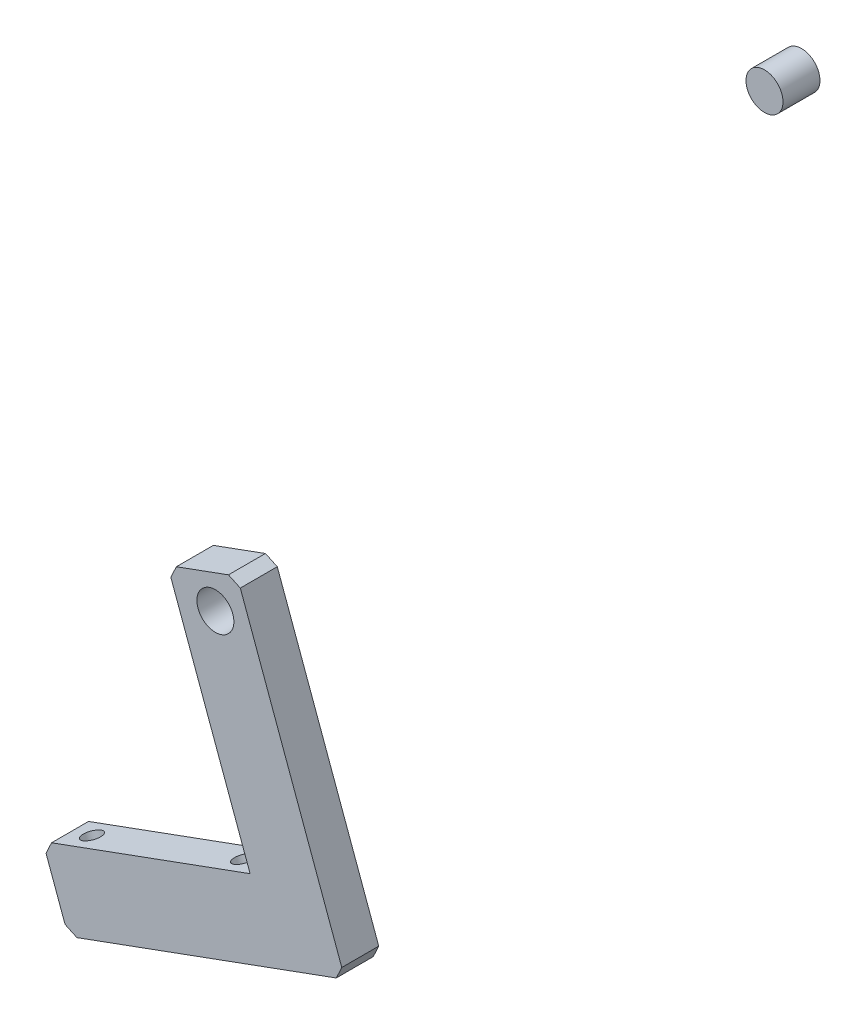
SolidWorks part; units mm, degrees
ref_plane "前基準面" through (0, 0, 0) normal (0, 0, 1) x (1, 0, 0)
ref_plane "上基準面" through (0, 0, 0) normal (0, 1, 0) x (1, 0, 0)
ref_plane "右基準面" through (0, 0, 0) normal (1, 0, 0) x (0, 0, -1)
sketch "草圖1" plane through (0, 0, 0) normal (0, 0, 1) x (1, 0, 0)
  line L0 (-29.9561, 9.7552) -> (-48.7426, 2.8947)
  line L2 (-48.7426, 2.8947) -> (-26.446, -58.1615)
  line L3 (-26.446, -58.1615) -> (-82.4902, -78.6278)
  line L4 (-82.4902, -78.6278) -> (-75.6297, -97.4144)
  line L5 (-75.6297, -97.4144) -> (-0.799, -70.0876)
  line L6 (-0.799, -70.0876) -> (-29.9561, 9.7552)
  circle A0 centre (-35.8357, -1.3461) radius 5
  circle A1 centre (112.659, 194.6505) radius 5
  dimension "D4" = 10
  dimension "D5" = 10
  dimension "D1" = 20
  dimension "D2" = 20
  dimension "D3" = 65
extrude "填料-伸長1" add sketch "草圖1" along normal blind 10
sketch "草圖2" plane through (15.6286, -42.7967, 0) normal (-0.343, 0.9393, 0) x (0.9393, 0.343, 0)
  circle A0 centre (-95.6715, -4.9822) radius 2.5
  circle A1 centre (-52.1263, -4.9822) radius 2.5
  dimension "D1" = 5
  dimension "D2" = 5
extrude "除料-伸長2" cut sketch "草圖2" against normal through all
chamfer "導角1" distance 2.5 angle 45 5 edges at (-29.9561, 9.7552, 5) (-48.7426, 2.8947, 5) (-0.799, -70.0876, 5) (-75.6297, -97.4144, 5) (-82.4902, -78.6278, 5)
